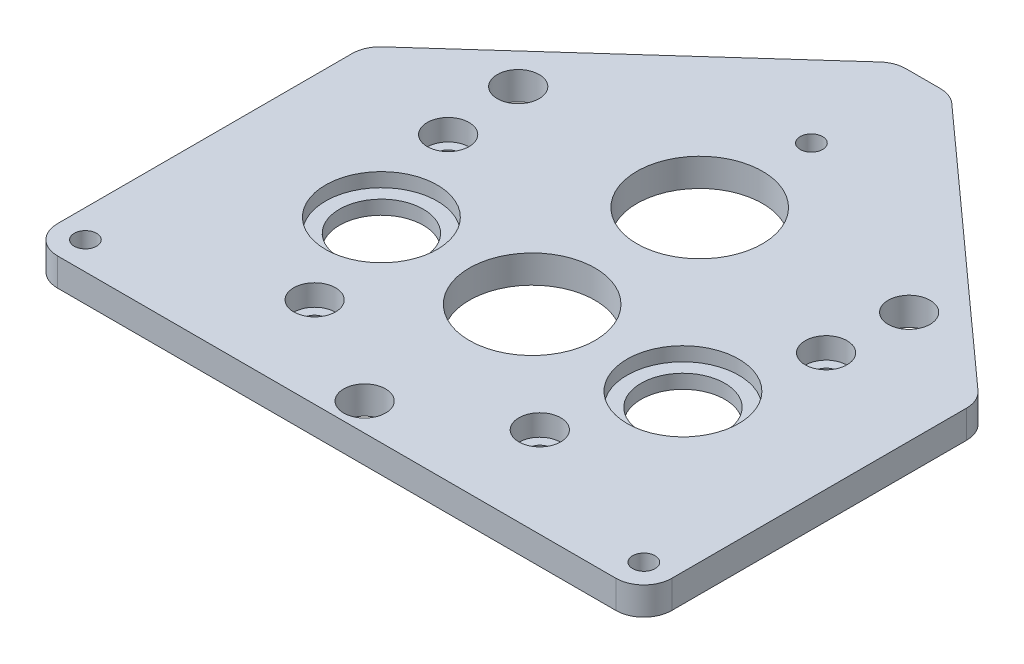
SolidWorks part; units mm, degrees
material "6061-T6 (SS)"
ref_plane "Front Plane" through (0, 0, 0) normal (0, 0, 1) x (1, 0, 0)
ref_plane "Top Plane" through (0, 0, 0) normal (0, 1, 0) x (1, 0, 0)
ref_plane "Right Plane" through (0, 0, 0) normal (1, 0, 0) x (0, 0, -1)
sketch "Sketch1" plane through (0, 0, 0) normal (0, 1, 0) x (1, 0, 0)
  line L0 (0, 0) -> (0, -19.05) construction
  line L1 (69.85, -19.05) -> (69.85, 57.15)
  line L2 (69.85, 57.15) -> (6.35, 114.3)
  line L3 (6.35, 114.3) -> (-6.35, 114.3)
  line L4 (-6.35, 114.3) -> (-69.85, 57.15)
  line L5 (-69.85, 57.15) -> (-69.85, -19.05)
  line L8 (-69.85, -19.05) -> (69.85, -19.05)
  dimension "D7" = 139.7
  dimension "D1" = 57.15
  dimension "D2" = 114.3
  dimension "D3" = 12.7
  dimension "D4" = 19.05
extrude "Boss-Extrude1" add sketch "Sketch1" along normal blind 6.35
sketch "Sketch2" plane through (0, 6.35, 0) normal (0, 1, 0) x (1, 0, 0)
  line L0 (-34.29, 25.4) -> (0, 0) construction
  line L2 (0, 0) -> (34.29, 25.4) construction
  circle A0 centre (-34.29, 25.4) radius 9.525
  circle A1 centre (34.29, 25.4) radius 9.525
  dimension "D1" = 19.05
  dimension "D2" = 68.58
  dimension "D3" = 25.4
extrude "Motor Shaft Holes" cut sketch "Sketch2" against normal through all
sketch "Sketch3" plane through (0, 6.35, 0) normal (0, 1, 0) x (1, 0, 0)
  line L0 (-34.29, 25.4) -> (34.29, 25.4) construction
  circle A0 centre (0, 25.4) radius 14.2875
  dimension "D1" = 28.575
extrude "First Bearing Hole" cut sketch "Sketch3" against normal through all
sketch "Sketch4" plane through (0, 6.35, 0) normal (0, 1, 0) x (1, 0, 0)
  circle A0 centre (-34.29, 25.4) radius 12.7
  circle A1 centre (34.29, 25.4) radius 12.7
  dimension "D1" = 25.4
extrude "Pinion Clearance" cut sketch "Sketch4" against normal blind 3.175
sketch "Sketch5" plane through (0, 6.35, 0) normal (0, 1, 0) x (1, 0, 0)
  circle A0 centre (0, 63.5) radius 14.2875
  circle A1 centre (0, 25.4) radius 14.2875 construction
  dimension "D1" = 28.575
  dimension "D2" = 38.1
extrude "Cut-Extrude1" cut sketch "Sketch5" against normal through all contours A0
hole_wizard "CBORE for #10 Socket Head Cap Screw1" positions "Sketch6" profile "Sketch7" counterbore size "#10" standard "ANSI Inch" end condition through all
sketch "Sketch6" plane through (0, 6.35, 0) normal (0, 1, 0) x (1, 0, 0)
  line L0 (-25.6027, 1.5318) -> (-42.9773, 49.2682) construction
  line L1 (-69.85, 57.15) -> (-69.85, -19.05) construction
  circle A0 centre (-34.29, 25.4) radius 25.4
  point P5 (-25.6027, 1.5318)
  point P6 (-42.9773, 49.2682)
  dimension "D1" = 50.8
  dimension "D2" = 20
sketch "Sketch7" plane through (-42.9773, 6.35, -49.2682) normal (1, 0, 0) x (0, 0, 1)
  line L0 (0, 0) -> (0, 6.35)
  line L1 (0, 6.35) -> (2.5527, 6.35)
  line L3 (2.5527, 6.35) -> (2.5527, 4.826)
  line L4 (2.5527, 4.826) -> (4.7625, 4.826)
  line L5 (4.7625, 4.826) -> (4.7625, 0)
  line L7 (4.7625, 0) -> (0, 0)
  line L11 (0, -6.35) -> (0, 107.95) construction
  dimension "Thru Hole Dia." = 5.1054
  dimension "Thru Hole Depth" = 6.35
  dimension "C'Bore Dia." = 9.525
  dimension "C'Bore Depth" = 4.826
mirror "Mirror1" about plane through (0, 0, 0) normal (1, 0, 0) of "CBORE for #10 Socket Head Cap Screw1"
sketch "Sketch8" plane through (0, 6.35, 0) normal (0, 1, 0) x (1, 0, 0)
  line L0 (-34.29, -7.9375) -> (34.29, -7.9375)
  line L1 (-69.85, 57.15) -> (-69.85, -19.05) construction
  circle A0 centre (-34.29, 25.4) radius 33.3375
  circle A1 centre (34.29, 25.4) radius 33.3375
  dimension "D1" = 66.675
  dimension "D2" = 35.56
  dimension "D3" = 68.58
hole_wizard "#10 Clearance Hole1" positions "Sketch9" profile "Sketch10" hole size "#10" standard "ANSI Inch" end condition through all
sketch "Sketch9" plane through (0, 34.925, 19.05) normal (0, 1, 0) x (1, 0, 0)
  point P0 (-63.5, 6.35)
  point P2 (63.5, 6.35)
  point P13 (0, 107.95)
sketch "Sketch10" plane through (-63.5, 34.925, 12.7) normal (1, 0, 0) x (0, 0, 1)
  line L0 (0, 0) -> (0, 34.925)
  line L1 (0, 34.925) -> (2.5527, 34.925)
  line L2 (2.5527, 34.925) -> (2.5527, 0)
  line L3 (2.5527, 0) -> (0, 0)
  line L4 (0, -6.35) -> (0, 107.95) construction
  dimension "Thru Hole Dia." = 5.1054
  dimension "Thru Hole Depth" = 34.925
fillet "Fillet1" radius 6.35 6 edges at (-69.85, 3.175, -57.15) (-6.35, 3.175, -114.3) (6.35, 3.175, -114.3) (69.85, 3.175, -57.15) (69.85, 3.175, 19.05) (-69.85, 3.175, 19.05)
extrude "Cut-Extrude2" cut sketch "Sketch11" against normal blind 50.8
sketch "Sketch11" plane through (0, 0, 19.05) normal (0, -1, 0) x (-1, 0, 0)
  circle A0 centre (-44.45, 85.725) radius 4.7625
  circle A1 centre (44.45, 85.725) radius 4.7625
  circle A2 centre (0, 6.35) radius 4.7625
